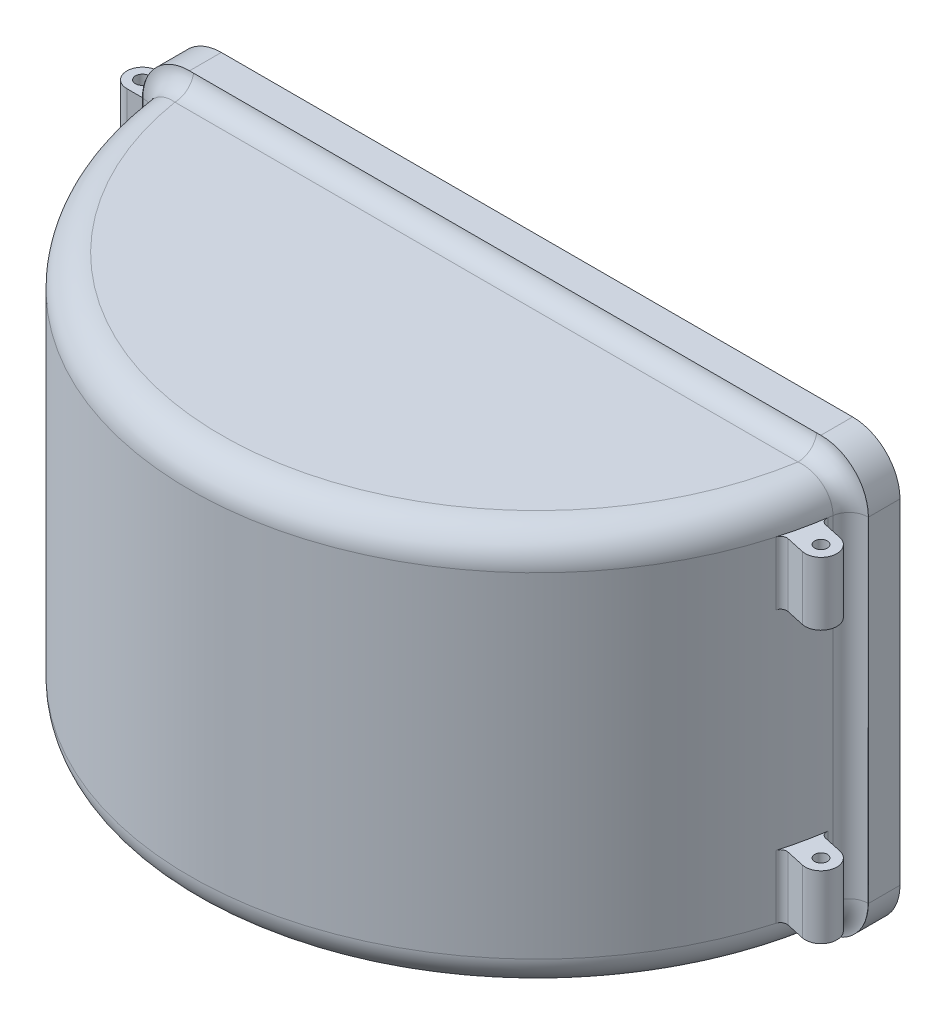
SolidWorks part; units mm, degrees
ref_plane "Front Plane" through (0, 0, 0) normal (0, 0, 1) x (1, 0, 0)
ref_plane "Top Plane" through (0, 0, 0) normal (0, 1, 0) x (1, 0, 0)
ref_plane "Right Plane" through (0, 0, 0) normal (1, 0, 0) x (0, 0, -1)
sketch "Sketch1" plane through (0, 0, 0) normal (0, 1, 0) x (1, 0, 0)
  line L0 (-110, 0) -> (110, 0)
  arc A1 (-110, 0) -> (110, 0) centre (0, 0) ccw
extrude "Boss-Extrude1" add sketch "Sketch1" along normal blind 126
sketch "Sketch2" plane through (0, 0, 0) normal (0, 1, 0) x (1, 0, 0)
  line L0 (-107, 0) -> (107, 0)
  arc A1 (-107, 0) -> (107, 0) centre (0, 0) ccw
extrude "Cut-Extrude1" cut sketch "Sketch2" along normal offset from surface (120 mm away) 3 from offset 3 up to face at (0, 126, 55)
fillet "Fillet1" radius 7 2 edges at (0, 123, 107) (0, 3, 107)
fillet "Fillet2" radius 10 2 edges at (0, 0, 110) (0, 126, 110)
sketch "Sketch3" plane through (0, 0, 0) normal (0, 0, -1) x (-1, 0, 0)
  line L2 (-107, 10) -> (-107, 116)
  line L4 (-100, 123) -> (100, 123)
  line L6 (107, 116) -> (107, 10)
  line L8 (100, 3) -> (-100, 3)
  line L10 (-115, 10) -> (-115, 116)
  line L12 (-100, 131) -> (100, 131)
  line L14 (115, 116) -> (115, 10)
  line L16 (100, -5) -> (-100, -5)
  arc A0 (-107, 10) -> (-100, 3) centre (-100, 10) ccw
  arc A1 (-100, 123) -> (-107, 116) centre (-100, 116) ccw
  arc A2 (100, 3) -> (107, 10) centre (100, 10) ccw
  arc A3 (107, 116) -> (100, 123) centre (100, 116) ccw
  arc A4 (115, 116) -> (100, 131) centre (100, 116) ccw
  arc A5 (100, -5) -> (115, 10) centre (100, 10) ccw
  arc A6 (-115, 10) -> (-100, -5) centre (-100, 10) ccw
  arc A7 (-100, 131) -> (-115, 116) centre (-100, 116) ccw
extrude "Boss-Extrude2" add sketch "Sketch3" against normal blind 10
sketch "Sketch4" plane through (0, 0, 0) normal (0, 1, 0) x (1, 0, 0)
  line L4 (-120, -9.9) -> (-115, -9.9)
  line L8 (-120, -0.1) -> (-115, -0.1)
  line L9 (-115, -0.1) -> (-115, -9.9)
  circle A1 centre (-120, -5) radius 2.2
  arc A2 (-120, -0.1) -> (-120, -9.9) centre (-120, -5) ccw
sketch "Sketch6" plane through (0, 0, 0) normal (0, 1, 0) x (1, 0, 0)
  line L8 (113.9379, -29.8859) -> (106.3162, -28.229)
  line L10 (116.0621, -20.1141) -> (108.4404, -18.4572)
  circle A0 centre (115, -25) radius 2
  arc A4 (113.9379, -29.8859) -> (116.0621, -20.1141) centre (115, -25) ccw
  arc A6 (106.3162, -28.229) -> (108.4404, -18.4572) centre (0, 0) ccw
sketch "Sketch7" plane through (0, 3, 0) normal (0, 1, 0) x (1, 0, 0)
  line L0 (12.5, 0) -> (5.2, 0)
  line L2 (-5.2, 0) -> (-12.5, 0)
  arc A0 (-5.2, 0) -> (5.2, 0) centre (0, 0) ccw
  arc A1 (-12.5, 0) -> (12.5, 0) centre (0, 0) ccw
extrude "Boss-Extrude7" add sketch "Sketch7" along normal blind 5
extrude "Boss-Extrude8" add sketch "Sketch7<2>" against normal blind 5 from surface starting at face at (0, 123, 50)
sketch "Sketch7<2>" plane through (0, 3, 0) normal (0, 1, 0) x (1, 0, 0) same geometry as "Sketch7"
extrude "Boss-Extrude9" add sketch "Sketch6" along normal blind 20 from vertex starting at point (109.5445, 10, 10)
extrude "Boss-Extrude10" add sketch "Sketch6<3>" against normal blind 20 from vertex starting at point (109.5445, 116, 10)
sketch "Sketch6<3>" plane through (0, 0, 0) normal (0, 1, 0) x (1, 0, 0) same geometry as "Sketch6"
extrude "Boss-Extrude11" add sketch "Sketch4" along normal blind 27.3 from vertex starting at point (-115, 10, 10)
extrude "Boss-Extrude12" add sketch "Sketch4<3>" against normal blind 27.3 from vertex starting at point (-115, 116, 10)
sketch "Sketch4<3>" plane through (0, 0, 0) normal (0, 1, 0) x (1, 0, 0) same geometry as "Sketch4"
fillet "Fillet3" radius 2 6 edges at (0, 123, 12.5) (0, 3, 12.5) (108.4404, 20, 18.4572) (108.4404, 106, 18.4572) (106.3162, 106, 28.229) (106.3162, 20, 28.229)
fillet "Fillet4" radius 6 2 edges at (-109.5445, 63, 10) (109.5445, 63, 10)
